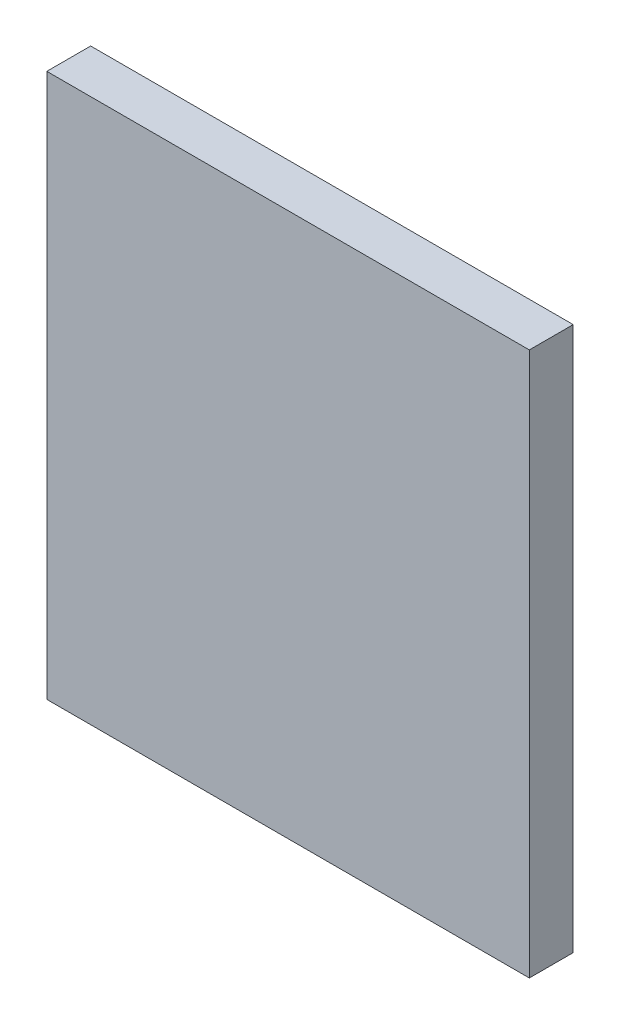
SolidWorks part; units mm, degrees
material "Бальса"
ref_plane "Спереди" through (0, 0, 0) normal (0, 0, 1) x (1, 0, 0)
ref_plane "Сверху" through (0, 0, 0) normal (0, 1, 0) x (1, 0, 0)
ref_plane "Справа" through (0, 0, 0) normal (1, 0, 0) x (0, 0, -1)
sketch "Эскиз1" plane through (0, 0, 0) normal (0, 0, 1) x (1, 0, 0)
  line L1 (0, 0) -> (550, 0)
  line L2 (0, 0) -> (0, 620)
  line L3 (0, 620) -> (550, 620)
  line L4 (550, 0) -> (550, 620)
  dimension "D1" = 550
  dimension "D2" = 620
extrude "Бобышка-Вытянуть1" add sketch "Эскиз1" along normal blind 50
